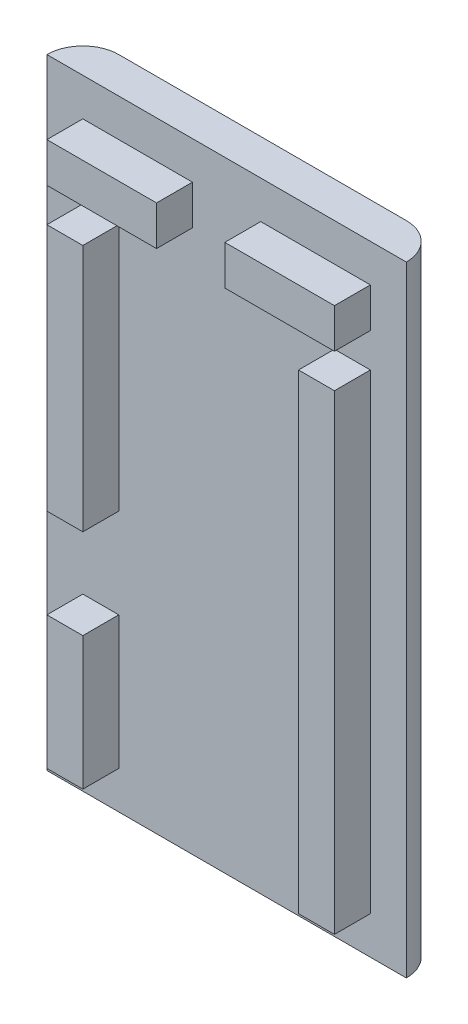
SolidWorks part; units mm, degrees
ref_plane "Front Plane" through (0, 0, 0) normal (1, 0, 0) x (0, 1, 0)
ref_plane "Top Plane" through (0, 0, 0) normal (0, 0, 1) x (0, 1, 0)
ref_plane "Right Plane" through (0, 0, 0) normal (0, 1, 0) x (-1, 0, 0)
sketch "Sketch1" plane through (0, 0, 0) normal (0, 0, 1) x (0, 1, 0)
  line L1 (-17.25, 10) -> (17.25, 10)
  line L2 (-17.25, 10) -> (-17.25, -10)
  line L3 (-17.25, -10) -> (17.25, -10)
  line L4 (17.25, 10) -> (17.25, -10)
  line L5 (-17.25, 10) -> (17.25, -10) construction
  line L6 (-17.25, -10) -> (17.25, 10) construction
  point P0 (0, 0)
  dimension "D1" = 20
  dimension "D2" = 34.5
extrude "Boss-Extrude1" add sketch "Sketch1" along normal blind 2
fillet "Fillet1" radius 2 2 edges at (-10, 0, 0) (10, 0, 0)
sketch "Sketch2" plane through (0, 0, 2) normal (0, 0, 1) x (1, 0, 0)
  line L0 (10, 17.25) -> (-10, 17.25) construction
  line L1 (-8, 15.15) -> (8, 15.15)
  line L2 (-8, 15.15) -> (-8, 12.95)
  line L3 (-8, -15.15) -> (-6, -15.15)
  line L4 (8, 15.15) -> (8, 12.95)
  line L5 (-8, 15.15) -> (8, -15.15) construction
  line L6 (-8, -15.15) -> (8, 15.15) construction
  line L7 (10, -17.25) -> (10, 17.25) construction
  line L10 (-6, -15.15) -> (-6, -7.75)
  line L12 (6, -15.15) -> (6, 11.05)
  line L13 (-6, 11.05) -> (-8, 11.05)
  line L14 (6, -15.15) -> (8, -15.15)
  line L19 (6, 11.05) -> (8, 11.05)
  line L20 (-8, 12.95) -> (8, 12.95)
  line L21 (-8, 11.05) -> (-8, -2.75)
  line L22 (8, 11.05) -> (8, -15.15)
  line L27 (-7.0155, -17.25) -> (-7.0155, -7.75) construction
  line L28 (-10, -17.25) -> (10, -17.25) construction
  line L29 (-8, -7.75) -> (-6, -7.75)
  line L30 (-8, -2.75) -> (-6, -2.75)
  line L31 (-8, -7.75) -> (-8, -15.15)
  line L32 (-6, -2.75) -> (-6, 11.05)
  point P0 (0, 0)
  dimension "D1" = 2.1
  dimension "D2" = 2
  dimension "D3" = 2
  dimension "D4" = 2
  dimension "D5" = 2.2
  dimension "D6" = 1.9
  dimension "D7" = 1.9
  dimension "D8" = 9.5
  dimension "D9" = 5
extrude "Boss-Extrude2" add sketch "Sketch2" along normal blind 2
sketch "Sketch3" plane through (0, 0, 0) normal (1, 0, 0) x (0, 1, 0)
  line L1 (12.95, 4) -> (15.15, 4)
  line L2 (12.95, 4) -> (12.95, 2)
  line L3 (12.95, 2) -> (15.15, 2)
  line L4 (15.15, 4) -> (15.15, 2)
extrude "Cut-Extrude1" cut sketch "Sketch3" against normal blind 1.9 and the other way blind 1.9
